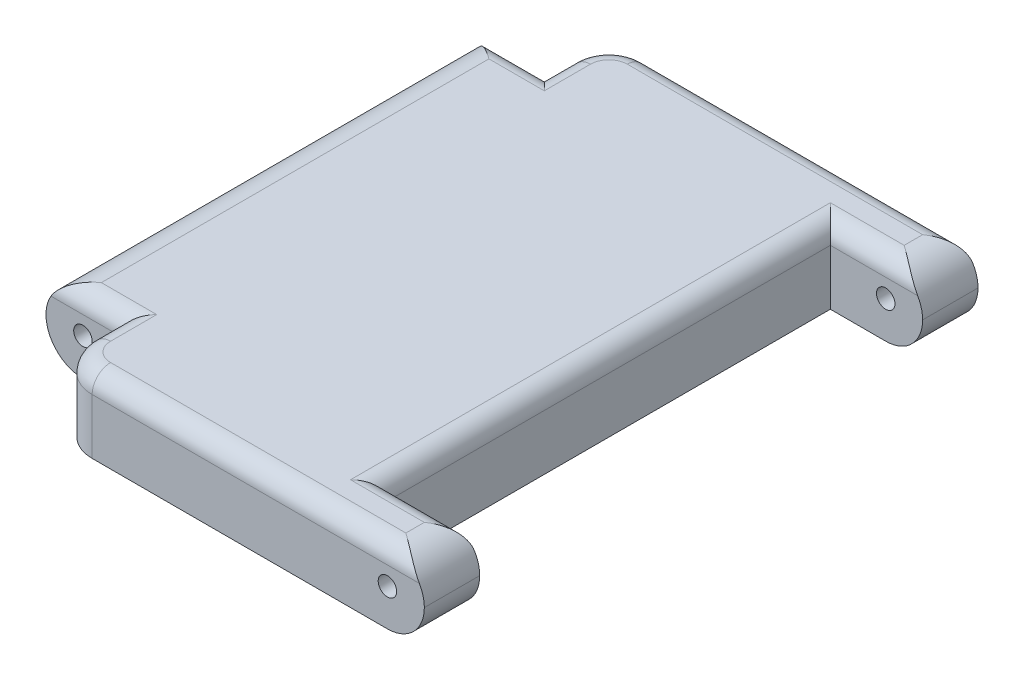
SolidWorks part; units mm, degrees
ref_plane "Спереди" through (0, 0, 0) normal (0, 0, 1) x (1, 0, 0)
ref_plane "Сверху" through (0, 0, 0) normal (0, 1, 0) x (1, 0, 0)
ref_plane "Справа" through (0, 0, 0) normal (1, 0, 0) x (0, 0, -1)
sketch "Эскиз1" plane through (0, 0, 0) normal (0, 1, 0) x (1, 0, 0)
  line L0 (0, 0) -> (-10, 0) construction
  line L1 (-10, 15) -> (10, 15)
  line L2 (-10, 15) -> (-10, 11.5)
  line L3 (-10, -15) -> (10, -15)
  line L4 (10, 15) -> (10, 12)
  line L5 (-10, 15) -> (10, -15) construction
  line L6 (-10, -15) -> (10, 15) construction
  line L7 (-10, 11.5) -> (-14, 11.5)
  line L8 (-14, 11.5) -> (-14, -11.5)
  line L9 (-14, -11.5) -> (-10, -11.5)
  line L10 (10, 12) -> (5, 12)
  line L11 (5, 12) -> (5, -12)
  line L12 (5, -12) -> (10, -12)
  line L13 (10, -12) -> (10, -15)
  line L14 (-10, -11.5) -> (-10, -15)
  point P0 (0, 0)
  dimension "D1" = 30
  dimension "D2" = 23
  dimension "D3" = 4
  dimension "D4" = 20
  dimension "D5" = 5
  dimension "D6" = 24
extrude "Бобышка-Вытянуть1" add sketch "Эскиз1" along normal blind 4
sketch "Эскиз2" plane through (0, 0, -12) normal (0, 0, 1) x (1, 0, 0)
  line L0 (10, 4) -> (10, 0) construction
  circle A0 centre (8, 2) radius 0.5
  point P2 (0, 0)
  point P5 (10, 2)
  dimension "D2" = 1
  dimension "D1" = 2
extrude "Вырез-Вытянуть1" cut sketch "Эскиз2" against normal through all both and the other way through all
sketch "Эскиз3" plane through (0, 0, 11.5) normal (0, 0, 1) x (1, 0, 0)
  line L0 (-14, 4) -> (-14, 0) construction
  line L1 (-14, 0) -> (-10, 0) construction
  circle A0 centre (-12, 2) radius 0.5
  point P2 (0, 0)
  point P5 (-14, 2)
  point P6 (0, 0)
  point P9 (-12, 0)
  dimension "D1" = 1
extrude "Вырез-Вытянуть2" cut sketch "Эскиз3" against normal up to next
fillet "Скругление1" radius 2 8 edges at (10, 0, -13.5) (10, 4, -13.5) (10, 0, 13.5) (10, 4, 13.5) (-14, 0, 0) (-14, 4, 0) (-10, 2, -15) (-10, 2, 15)
fillet "Скругление2" radius 1 11 edges at (5, 4, 0) (6.5, 4, 12) (0, 4, 15) (-9.4142, 4, 14.4142) (-10, 4, 12.25) (-11, 4, 11.5) (-11, 4, -11.5) (-10, 4, -12.25) (-9.4142, 4, -14.4142) (0, 4, -15) (6.5, 4, -12)
